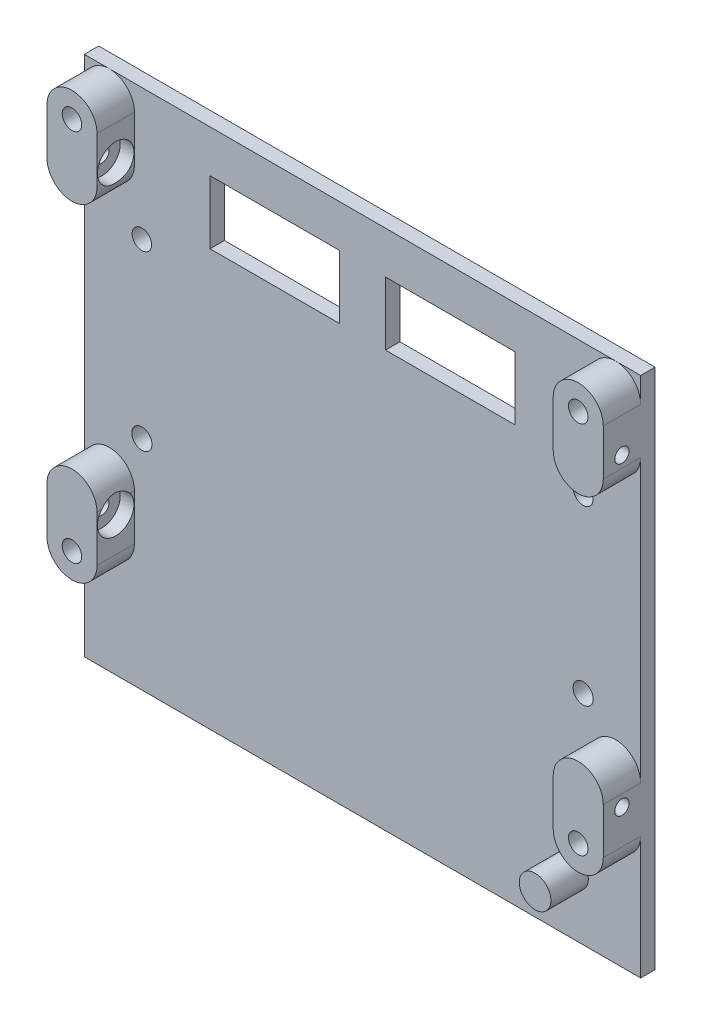
SolidWorks part; units mm, degrees
material "ABS"
ref_plane "Top Plane" through (0, 0, 0) normal (0, 0, 1) x (1, 0, 0)
ref_plane "Front Plane" through (0, 0, 0) normal (0, 1, 0) x (1, 0, 0)
ref_plane "Right Plane" through (0, 0, 0) normal (1, 0, 0) x (0, 0, -1)
sketch "Back Plate Sketch" plane through (0, 0, 0) normal (0, 0, 1) x (1, 0, 0)
  line L0 (-4, 38) -> (-4, 27)
  line L1 (-48.35, -45.35) -> (48.35, -45.35)
  line L2 (-48.35, -45.35) -> (-48.35, 45.35)
  line L3 (-48.35, 45.35) -> (48.35, 45.35)
  line L4 (48.35, -45.35) -> (48.35, 45.35)
  line L5 (-48.35, -45.35) -> (48.35, 45.35) construction
  line L6 (-48.35, 45.35) -> (48.35, -45.35) construction
  line L15 (-4, 27) -> (-26.5, 27)
  line L16 (-26.5, 38) -> (-26.5, 27)
  line L17 (-4, 38) -> (-26.5, 38)
  line L18 (26.5, 38) -> (4, 38)
  line L19 (4, 38) -> (4, 27)
  line L20 (26.5, 27) -> (4, 27)
  line L21 (26.5, 38) -> (26.5, 27)
  line L22 (0, 43.5) -> (0, 45.35) construction
  line L23 (-46.5, 43.5) -> (46.5, 43.5) construction
  line L24 (-46.5, 43.5) -> (-46.5, -43.5) construction
  line L25 (-46.5, -43.5) -> (46.5, -43.5) construction
  line L26 (46.5, 43.5) -> (46.5, -43.5) construction
  line L27 (0, -43.5) -> (0, 43.5) construction
  line L28 (-46.5, 0) -> (46.5, 0) construction
  line L29 (46.5, 0) -> (48.35, 0) construction
  line L30 (-4, 32.5) -> (4, 32.5) construction
  line L32 (-42.4123, 38.25) -> (-40.8246, 41) construction
  line L33 (-40.8246, 41) -> (-42.4123, 43.75) construction
  line L34 (-42.4123, 43.75) -> (-45.5877, 43.75) construction
  line L35 (-45.5877, 43.75) -> (-47.1754, 41) construction
  line L36 (-47.1754, 41) -> (-45.5877, 38.25) construction
  line L37 (-45.5877, 38.25) -> (-42.4123, 38.25) construction
  circle A0 centre (-44, 41) radius 3.1754
  circle A1 centre (44, 41) radius 3.1754
  circle A2 centre (-44, -24) radius 3.1754
  circle A3 centre (44, -24) radius 3.1754
  circle A4 centre (-38.35, 22.5) radius 1.7
  circle A5 centre (-38.35, -7.5) radius 1.7572
  circle A6 centre (38.35, -7.5) radius 1.7572
  circle A7 centre (38.35, 22.5) radius 1.7
  point P0 (0, 0)
  point P10 (0, 32.5)
  point P41 (0, 0)
  point P44 (-39.5429, 22.0227)
  point P49 (0, 0)
  point P50 (-40.8246, 25)
  point P186 (0, 0)
  dimension "D13" = 3.4
  dimension "D4" = 22.5
  dimension "D5" = 11
  dimension "D8" = 8
  dimension "D9" = 93
  dimension "D10" = 87
  dimension "D2" = 1.85
  dimension "D3" = 5.5
  dimension "D6" = 5.5
  dimension "D7" = 2.5
  dimension "D11" = 88
  dimension "D12" = 65
  dimension "D14" = 30
  dimension "D15" = 22.5
  dimension "D16" = 10
extrude "Back Plate" add sketch "Back Plate Sketch" against normal blind 2.5
sketch "Stand Offs Sketch" plane through (0, 0, 0) normal (0, 0, 1) x (1, 0, 0)
  line L1 (-46.5, 43.5) -> (46.5, 43.5) construction
  line L2 (-46.5, 43.5) -> (-46.5, -43.5) construction
  line L3 (-46.5, -43.5) -> (46.5, -43.5) construction
  line L4 (46.5, 43.5) -> (46.5, -43.5) construction
  line L5 (0, -43.5) -> (0, 43.5) construction
  line L6 (-46.5, 0) -> (46.5, 0) construction
  line L7 (-39.65, 33) -> (-39.65, 41)
  line L8 (-48.35, 41) -> (-48.35, 33)
  line L9 (-46.5, 8.5) -> (46.5, 8.5) construction
  line L16 (48.35, 41) -> (48.35, 33)
  line L18 (39.65, 33) -> (39.65, 41)
  line L19 (39.65, -16) -> (39.65, -24)
  line L21 (48.35, -24) -> (48.35, -16)
  line L22 (-48.35, -24) -> (-48.35, -16)
  line L24 (-39.65, -16) -> (-39.65, -24)
  line L25 (-48.35, 45.35) -> (-48.35, -45.35) construction
  circle A0 centre (-44, 41) radius 1.7
  arc A1 (-39.65, 41) -> (-48.35, 41) centre (-44, 41) ccw
  circle A8 centre (36.5, -35) radius 2.75
  circle A13 centre (44, 41) radius 1.7
  arc A14 (39.65, 41) -> (48.35, 41) centre (44, 41) cw
  circle A15 centre (44, -24) radius 1.7
  arc A16 (39.65, -24) -> (48.35, -24) centre (44, -24) ccw
  arc A17 (-39.65, -24) -> (-48.35, -24) centre (-44, -24) cw
  circle A18 centre (-44, -24) radius 1.7
  arc A19 (-48.35, 33) -> (-39.65, 33) centre (-44, 33) ccw
  arc A20 (-48.35, -16) -> (-39.65, -16) centre (-44, -16) cw
  arc A21 (48.35, -16) -> (39.65, -16) centre (44, -16) ccw
  arc A22 (48.35, 33) -> (39.65, 33) centre (44, 33) cw
  point P37 (-39.09, 29.0033)
  point P38 (-40.2733, 29.004)
  point P92 (0, 0)
  dimension "D3" = 3.4
  dimension "D8" = 5.5
  dimension "D1" = 93
  dimension "D2" = 87
  dimension "D5" = 2.5
  dimension "D6" = 88
  dimension "D10" = 8.5
  dimension "D7" = 32.5
  dimension "D9" = 10
  dimension "D4" = 8
extrude "Stand Offs" add sketch "Stand Offs Sketch" along normal blind 6.5
chamfer "PCB Nut No Support Chamfer" distance 1.5 angle 45 4 edges at (-42.3, 41, 0) (-45.7, -24, 0) (45.7, -24, 0) (42.3, 41, 0)
fillet "Corner Fillets" [suppressed] radius 2
sketch "Top Connectors Sketch" plane through (0, 0, 0) normal (1, 0, 0) x (0, 0, -1)
  line L0 (0, 8.5) -> (5, 8.5) construction
  line L1 (0, 43.5) -> (5, 43.5) construction
  line L2 (0, 41) -> (5, 41) construction
  circle A0 centre (-3.25, 35) radius 1.25
  circle A1 centre (-3.25, -18) radius 1.25
  dimension "D7" = 32.5
  dimension "D1" = 2.5
  dimension "D2" = 35
  dimension "D3" = 3.25
  dimension "D4" = 5
  dimension "D5" = 43.5
  dimension "D6" = 2.5
extrude "Top Connectors Cut" cut sketch "Top Connectors Sketch" against normal through all and the other way through all
sketch "Top Connectors Nut Sketch" plane through (0, 0, 0) normal (1, 0, 0) x (0, 0, -1)
  line L0 (0, 8.5) -> (5, 8.5) construction
  line L1 (0, 43.5) -> (5, 43.5) construction
  line L2 (0, 41) -> (5, 41) construction
  line L4 (-4.8377, 32.25) -> (-1.6623, 32.25) construction
  line L5 (-1.6623, 32.25) -> (-0.0746, 35) construction
  line L6 (-0.0746, 35) -> (-1.6623, 37.75) construction
  line L7 (-1.6623, 37.75) -> (-4.8377, 37.75) construction
  line L8 (-4.8377, 37.75) -> (-6.4254, 35) construction
  line L9 (-6.4254, 35) -> (-4.8377, 32.25) construction
  circle A0 centre (-3.25, 35) radius 3.1754
  circle A1 centre (-3.25, -18) radius 3.1754
  point P9 (0, 0)
  dimension "D7" = 32.5
  dimension "D4" = 5
  dimension "D6" = 2.5
  dimension "D2" = 43.5
  dimension "D3" = 35
  dimension "D5" = 3.25
  dimension "D1" = 5.5
extrude "Top Connectors Left Nut Cut" cut sketch "Top Connectors Nut Sketch" against normal blind 2.4 from surface starting at face at (-39.65, 35, 4.5)
extrude "Top Connectors Right Nut Cut" cut sketch "Top Connectors Nut Sketch<2>" along normal blind 2.4 from surface starting at face at (39.65, 35, 2)
sketch "Top Connectors Nut Sketch<2>" plane through (0, 0, 0) normal (1, 0, 0) x (0, 0, -1) same geometry as "Top Connectors Nut Sketch"
equation "\"Controller Clearance\"= 2mm"
equation "\"Shell Thickness\"= 2.5"
equation "\"Screen Clearance\"= 1mm"
equation "\"PCB Hole Spacing X\"= 88mm"
equation "\"PCB Hole Spacing Y\"= 65mm"
equation "\"Controller Size X\"= 93mm"
equation "\"Controller Size Y\"= 87mm"
equation "\"Outside Fillet Radius\"= 2mm"
equation "\"Screen Height\"= 51.2mm"
equation "\"Screen Width\"= 78.6mm"
equation "\"SD Card Position\"= 22.5mm + 27/2.0mm + \"Shell Thickness\" + \"Controller Clearance\""
equation "\"SD Card Width\"= 31mm"
equation "\"D9@Back Plate Sketch\"=\"Controller Size X\""
equation "\"D10@Back Plate Sketch\"=\"Controller Size Y\""
equation "\"D2@Back Plate Sketch\"=\"Controller Clearance\"-\"Slip Fit Clearance\""
equation "\"D1@Corner Fillets\"=\"Outside Fillet Radius\""
equation "\"D1@Stand Offs Sketch\" = \"Controller Size X\""
equation "\"D2@Stand Offs Sketch\" = \"Controller Size Y\""
equation "\"D6@Stand Offs Sketch\" = \"PCB Hole Spacing X\""
equation "\"D1@Back Plate\"=\"Shell Thickness\""
equation "\"D1@Stand Offs\"=\"Standoff Height\""
equation "\"D7@Stand Offs Sketch\" = 0.5 * \"PCB Hole Spacing Y\""
equation "\"D5@Back Plate Sketch\"=2*\"Screen Clearance\"+9"
equation "\"D4@Back Plate Sketch\"=20.5+2*\"Screen Clearance\""
equation "\"D3@Back Plate Sketch\"=6.5-\"Screen Clearance\""
equation "\"Top Mounting Hole Position\"= 2.5mm"
equation "\"Top Connector Y Position\"= 0.5 * \"Controller Size Y\" - \"Top Mounting Hole Position\" - 6"
equation "\"D2@Top Connectors Sketch\" = \"Top Connector Y Position\""
equation "\"D3@Top Connectors Sketch\"=\"Standoff Height\"/2"
equation "\"D5@Top Connectors Sketch\" = \"Controller Size Y\" / 2"
equation "\"D6@Top Connectors Sketch\" = \"Top Mounting Hole Position\""
equation "\"D7@Top Connectors Sketch\" = \"PCB Hole Spacing Y\" / 2"
equation "\"Standoff Height\"= 9 - \"Shell Thickness\""
equation "\"Slip Fit Clearance\"= 0.15mm"
equation "\"D7@Back Plate Sketch\"=\"Top Mounting Hole Position\""
equation "\"D11@Back Plate Sketch\"=\"PCB Hole Spacing X\""
equation "\"D12@Back Plate Sketch\"=\"PCB Hole Spacing Y\""
equation "\"D6@Top Connectors Nut Sketch\" = \"Top Mounting Hole Position\""
equation "\"D7@Top Connectors Nut Sketch\" = \"PCB Hole Spacing Y\" / 2"
equation "\"D2@Top Connectors Nut Sketch\" = \"Controller Size Y\" / 2"
equation "\"D3@Top Connectors Nut Sketch\" = \"Top Connector Y Position\""
equation "\"D5@Top Connectors Nut Sketch\" = \"Standoff Height\" / 2"
